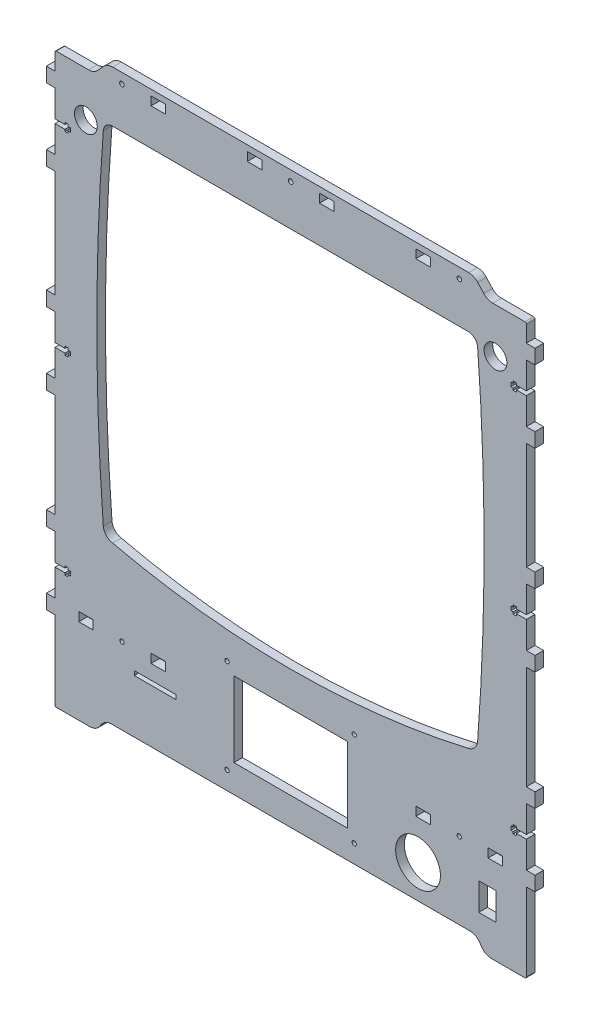
SolidWorks part; units mm, degrees
ref_plane "Спереди" through (0, 0, 0) normal (0, 0, 1) x (1, 0, 0)
ref_plane "Сверху" through (0, 0, 0) normal (0, 1, 0) x (1, 0, 0)
ref_plane "Справа" through (0, 0, 0) normal (1, 0, 0) x (0, 0, -1)
sketch "Эскиз1" plane through (0, 0, 0) normal (0, 0, 1) x (1, 0, 0)
  line L0 (-95.8892, 197.3491) -> (-85.8892, 197.3491)
  line L1 (-85.8892, 197.3491) -> (-85.8892, 191.3491)
  line L2 (-85.8892, 191.3491) -> (-95.8892, 191.3491)
  line L3 (-95.8892, 191.3491) -> (-95.8892, 197.3491)
  line L4 (97.3908, 191.3491) -> (87.3908, 191.3491)
  line L5 (87.3908, 191.3491) -> (87.3908, 197.3491)
  line L6 (87.3908, 197.3491) -> (97.3908, 197.3491)
  line L7 (97.3908, 197.3491) -> (97.3908, 191.3491)
  line L8 (97.3654, -142.8875) -> (87.3654, -142.8875)
  line L9 (87.3654, -142.8875) -> (87.3654, -136.6877)
  line L10 (87.3654, -136.6877) -> (97.3654, -136.6877)
  line L11 (97.3654, -136.6877) -> (97.3654, -142.8875)
  line L12 (147.3854, -142.8884) -> (137.3854, -142.8884)
  line L13 (137.3854, -142.8884) -> (137.3854, -136.6877)
  line L14 (137.3854, -136.6877) -> (147.3854, -136.6877)
  line L15 (147.3854, -136.6877) -> (147.3854, -142.8884)
  line L16 (-135.8946, -142.8871) -> (-145.8946, -142.8871)
  line L17 (-145.8946, -142.8871) -> (-145.8946, -136.6873)
  line L18 (-145.8946, -136.6873) -> (-135.8946, -136.6873)
  line L19 (-135.8946, -136.6873) -> (-135.8946, -142.8871)
  line L20 (-85.8746, -142.8871) -> (-95.8746, -142.8871)
  line L21 (-95.8746, -142.8871) -> (-95.8746, -136.6873)
  line L22 (-95.8746, -136.6873) -> (-85.8746, -136.6873)
  line L23 (-85.8746, -136.6873) -> (-85.8746, -142.8871)
  line L24 (-19.2392, 191.3491) -> (-29.2392, 191.3491)
  line L25 (-29.2392, 191.3491) -> (-29.2392, 197.3491)
  line L26 (-29.2392, 197.3491) -> (-19.2392, 197.3491)
  line L27 (-19.2392, 197.3491) -> (-19.2392, 191.3491)
  line L28 (30.7408, 191.3491) -> (20.7408, 191.3491)
  line L29 (20.7408, 191.3491) -> (20.7408, 197.3491)
  line L30 (20.7408, 197.3491) -> (30.7408, 197.3491)
  line L31 (30.7408, 197.3491) -> (30.7408, 191.3491)
  line L32 (-122.3991, 165.873) -> (123.6241, 165.873)
  line L33 (40.0454, -173.6357) -> (40.0454, -121.6361)
  line L34 (40.0454, -121.6361) -> (-38.5546, -121.6361)
  line L35 (-38.5546, -121.6361) -> (-38.5546, -173.6357)
  line L36 (-38.5546, -173.6357) -> (40.0454, -173.6357)
  line L37 (142.9388, -159.6762) -> (142.9388, -178.6762)
  line L38 (142.9388, -178.6762) -> (130.9388, -178.6762)
  line L39 (130.9388, -178.6762) -> (130.9388, -159.6762)
  line L40 (130.9388, -159.6762) -> (142.9388, -159.6762)
  line L41 (-162.3492, -146.9309) -> (-168.3546, -146.9309)
  line L42 (-168.3546, -146.9309) -> (-168.3546, -136.9309)
  line L43 (-168.3546, -136.9309) -> (-162.3546, -136.9309)
  line L44 (-162.3546, -136.9309) -> (-162.3546, -118.3209)
  line L45 (-162.3546, -96.9409) -> (-168.3546, -96.9409)
  line L46 (-168.3546, -96.9409) -> (-168.3546, -86.9409)
  line L47 (-168.3546, -86.9409) -> (-162.3546, -86.9409)
  line L48 (-162.3546, -86.9409) -> (-162.3546, -15.2109)
  line L49 (-162.3546, -15.2109) -> (-168.3546, -15.2109)
  line L50 (-162.3546, 34.7891) -> (-168.3546, 34.7891)
  line L51 (-168.3546, -5.2109) -> (-162.3546, -5.2109)
  line L52 (-168.3546, 44.7891) -> (-162.3546, 44.7891)
  line L56 (-162.3546, 128.9491) -> (-162.3546, 147.5491)
  line L57 (-162.3492, 168.9491) -> (-168.3492, 168.9491)
  line L58 (-168.3492, 168.9491) -> (-168.3492, 178.9491)
  line L59 (-168.3492, 178.9491) -> (-162.3492, 178.9491)
  line L60 (-162.3492, 178.9491) -> (-162.3492, 190.3491)
  line L61 (-162.3492, -200.9709) -> (-162.3492, -146.9309)
  line L62 (163.8454, -146.9309) -> (169.8454, -146.9309)
  line L63 (169.8454, -146.9309) -> (169.8454, -136.9309)
  line L64 (169.8454, -136.9309) -> (163.8513, -136.9309)
  line L65 (163.8513, -136.9309) -> (163.8513, -118.3209)
  line L66 (163.9392, -96.9409) -> (169.8512, -96.9409)
  line L67 (169.8512, -96.9409) -> (169.8512, -86.9409)
  line L68 (169.8512, -86.9409) -> (163.8512, -86.9409)
  line L69 (163.8512, -86.9409) -> (163.8512, -15.2109)
  line L70 (163.8512, -15.2109) -> (169.8512, -15.2109)
  line L71 (163.8512, 34.7891) -> (169.8512, 34.7891)
  line L72 (169.8512, -5.2109) -> (163.8512, -5.2109)
  line L73 (169.8512, 44.7891) -> (163.8512, 44.7891)
  line L74 (163.8512, 118.9491) -> (169.8512, 118.9491)
  line L75 (169.8512, 118.9491) -> (169.8512, 128.9491)
  line L76 (169.8512, 128.9491) -> (163.8512, 128.9491)
  line L77 (163.8512, 128.9491) -> (163.8512, 147.5491)
  line L78 (163.8508, 168.9491) -> (169.8508, 168.9491)
  line L79 (169.8508, 168.9491) -> (169.8508, 178.9491)
  line L80 (169.8508, 178.9491) -> (163.8508, 178.9491)
  line L81 (163.8508, 178.9491) -> (163.8508, 190.3491)
  line L82 (156.9388, 150.3491) -> (156.9388, 151.7492)
  line L83 (163.9392, -115.5209) -> (156.9392, -115.5209)
  line L84 (156.9392, -114.1224) -> (154.7382, -114.1224)
  line L85 (156.9399, -118.3209) -> (163.8513, -118.3209)
  line L86 (153.2384, -118.3222) -> (154.7405, -118.3222)
  line L87 (-155.4441, 11.989) -> (-153.2432, 11.989)
  line L88 (154.7382, -114.1224) -> (154.7382, -115.5222)
  line L89 (154.7391, 16.1893) -> (153.24, 16.1893)
  line L90 (153.2384, -115.5222) -> (153.2384, -118.3222)
  line L91 (-155.4426, -119.721) -> (-153.2418, -119.721)
  line L92 (163.8508, 150.3491) -> (156.9388, 150.3491)
  line L93 (156.9399, -119.7231) -> (156.9399, -118.3209)
  line L94 (156.9392, -115.5209) -> (156.9392, -114.1224)
  line L95 (154.7382, -115.5222) -> (153.2384, -115.5222)
  line L96 (154.741, 147.5502) -> (154.741, 146.1493)
  line L97 (-155.4451, -114.1209) -> (-155.4451, -115.5209)
  line L98 (154.7415, 13.3902) -> (154.7415, 11.9893)
  line L99 (-162.3546, 147.5491) -> (-155.4441, 147.5491)
  line L100 (-155.4441, 147.5491) -> (-155.4441, 146.149)
  line L101 (-155.4398, 150.3491) -> (-162.3492, 150.3491)
  line L102 (-153.2398, 150.3482) -> (-153.2398, 151.7491)
  line L103 (154.7405, -118.3222) -> (154.7405, -119.7231)
  line L104 (-155.4451, -115.5209) -> (-162.3546, -115.5209)
  line L105 (154.741, 151.7492) -> (154.741, 150.3493)
  line L106 (156.9417, 146.1493) -> (156.9417, 147.5491)
  line L107 (-153.2432, 13.3622) -> (-151.7428, 13.3622)
  line L108 (-155.4426, -118.3209) -> (-155.4426, -119.721)
  line L109 (153.241, 150.3493) -> (153.241, 147.5502)
  line L110 (-153.2451, 17.5891) -> (-155.4451, 17.5891)
  line L111 (-162.3546, 13.3891) -> (-155.4441, 13.3891)
  line L112 (154.741, 146.1493) -> (156.9417, 146.1493)
  line L113 (153.241, 147.5502) -> (154.741, 147.5502)
  line L114 (-153.2433, 147.5489) -> (-151.7375, 147.5489)
  line L115 (-151.7428, 13.3622) -> (-151.7428, 16.1885)
  line L116 (163.8512, 16.1891) -> (156.9392, 16.1891)
  line L117 (154.7391, 17.5621) -> (154.7391, 16.1893)
  line L118 (154.741, 150.3493) -> (153.241, 150.3493)
  line L119 (154.7415, 11.9893) -> (156.9417, 11.9893)
  line L120 (-153.2451, -114.1209) -> (-155.4451, -114.1209)
  line L121 (-151.7436, -118.3211) -> (-151.7436, -115.5218)
  line L122 (-153.2418, -118.3211) -> (-151.7436, -118.3211)
  line L123 (-153.2432, 11.989) -> (-153.2432, 13.3622)
  line L124 (156.9417, 13.3891) -> (163.8512, 13.3891)
  line L125 (-162.3546, -118.3209) -> (-155.4426, -118.3209)
  line L126 (153.24, 16.1893) -> (153.24, 13.3902)
  line L127 (-153.2451, -115.5218) -> (-153.2451, -114.1209)
  line L128 (-151.7428, 16.1885) -> (-153.2451, 16.1885)
  line L129 (-155.4441, 146.149) -> (-153.2433, 146.149)
  line L130 (-153.2418, -119.721) -> (-153.2418, -118.3211)
  line L131 (-155.4398, 151.7491) -> (-155.4398, 150.3491)
  line L132 (-151.7436, -115.5218) -> (-153.2451, -115.5218)
  line L133 (-153.2433, 146.149) -> (-153.2433, 147.5489)
  line L134 (153.24, 13.3902) -> (154.7415, 13.3902)
  line L135 (156.9388, 151.7492) -> (154.741, 151.7492)
  line L136 (-151.7375, 147.5489) -> (-151.738, 150.3482)
  line L137 (156.9417, 147.5491) -> (163.8512, 147.5491)
  line L138 (-155.4451, 16.1891) -> (-162.3546, 16.1891)
  line L139 (156.9417, 11.9893) -> (156.9417, 13.3891)
  line L140 (-155.4451, 17.5891) -> (-155.4451, 16.1891)
  line L141 (154.7405, -119.7231) -> (156.9399, -119.7231)
  line L142 (-153.2398, 151.7491) -> (-155.4398, 151.7491)
  line L143 (156.9392, 17.5621) -> (154.7391, 17.5621)
  line L144 (-151.738, 150.3482) -> (-153.2398, 150.3482)
  line L145 (-162.3546, -115.5209) -> (-162.3546, -96.9409)
  line L146 (-162.3492, 150.3491) -> (-162.3492, 168.9491)
  line L147 (163.9392, -115.5209) -> (163.9392, -96.9409)
  line L148 (163.8508, 150.3491) -> (163.8508, 168.9491)
  line L149 (-139.0924, 191.3491) -> (-161.5253, 191.3491)
  line L150 (-128.7242, 198.5879) -> (-132.8221, 194.1104)
  line L151 (123.9554, 201.3491) -> (-122.4539, 201.3491)
  line L152 (130.2257, 198.5879) -> (134.3236, 194.1104)
  line L153 (140.5939, 191.3491) -> (162.8508, 191.3491)
  line L154 (-131.8015, -198.9146) -> (-129.7448, -195.8949)
  line L155 (162.7628, -201.9477) -> (139.7264, -201.9477)
  line L156 (133.303, -198.9146) -> (131.2463, -195.8949)
  line L157 (-161.4373, -201.9509) -> (-138.3129, -201.9509)
  line L158 (-123.2334, -192.8586) -> (124.7349, -192.8586)
  line L159 (163.8454, -200.9731) -> (163.8454, -146.9309)
  line L160 (-162.3546, 13.3891) -> (-162.3546, -5.2109)
  line L161 (-168.3546, -15.2109) -> (-168.3546, -5.2109)
  line L162 (-168.3546, 34.7891) -> (-168.3546, 44.7891)
  line L163 (-162.3546, 44.7891) -> (-162.3546, 118.9491)
  line L164 (163.8512, 13.3891) -> (163.8512, -5.2109)
  line L165 (169.8512, -15.2109) -> (169.8512, -5.2109)
  line L166 (169.8512, 34.7891) -> (169.8512, 44.7891)
  line L167 (163.8512, 44.7891) -> (163.8512, 118.9491)
  line L168 (-155.4441, 13.3891) -> (-155.4441, 11.989)
  line L169 (-153.2451, 16.1885) -> (-153.2451, 17.5891)
  line L170 (156.9392, 16.1891) -> (156.9392, 17.5621)
  line L171 (-162.3546, 34.7891) -> (-162.3546, 16.1891)
  line L172 (163.8512, 34.7891) -> (163.8512, 16.1891)
  line L173 (-107.5042, -155.9271) -> (-107.5042, -152.9271)
  line L174 (-107.5042, -152.9271) -> (-78.5042, -152.9271)
  line L175 (-78.5042, -152.9271) -> (-78.5042, -155.9271)
  line L176 (-78.5042, -155.9271) -> (-107.5042, -155.9271)
  line L177 (-162.3546, 128.9491) -> (-168.3546, 128.9491)
  line L178 (-162.3546, 118.9491) -> (-168.3546, 118.9491)
  line L179 (-168.3546, 118.9491) -> (-168.3546, 128.9491)
  arc A0 (-122.4711, -84.0153) -> (123.6489, -84.0153) centre (0.5889, 449.8336) ccw
  arc A1 (-128.9341, 159.8968) -> (-128.9472, -76.974) centre (1428.6282, 41.3753) ccw
  arc A2 (130.1254, -76.9742) -> (130.1588, 159.8968) centre (-1430.5029, 41.6814) ccw
  circle A3 centre (44.7454, -115.1361) radius 1.5
  circle A4 centre (44.7454, -180.3857) radius 1.5
  circle A5 centre (-43.2546, -180.3857) radius 1.5
  circle A6 centre (-43.2546, -115.1361) radius 1.5
  circle A7 centre (88.8942, -169.8279) radius 15.5
  arc A8 (130.1588, 159.8968) -> (123.6241, 165.873) centre (123.6241, 159.3123) ccw
  arc A9 (-122.3991, 165.873) -> (-128.9341, 159.8968) centre (-122.472, 159.3916) ccw
  arc A10 (-128.9472, -76.974) -> (-122.4711, -84.0153) centre (-121.245, -76.3888) ccw
  arc A11 (123.6489, -84.0153) -> (130.1254, -76.9742) centre (121.7477, -75.7674) ccw
  circle A12 centre (0.7508, 194.3491) radius 1.6
  circle A13 centre (-116.0492, 194.3491) radius 1.6
  arc A14 (134.3236, 194.1104) -> (140.5939, 191.3491) centre (140.5939, 199.8491) ccw
  arc A15 (-161.5253, 191.3491) -> (-162.3492, 190.3491) centre (-161.4373, 190.4372) ccw
  arc A16 (-139.0924, 191.3491) -> (-132.8221, 194.1104) centre (-139.0924, 199.8491) ccw
  arc A17 (-122.4539, 201.3491) -> (-128.7242, 198.5879) centre (-122.4539, 192.8491) ccw
  circle A18 centre (117.5508, 194.3491) radius 1.6
  arc A19 (130.2257, 198.5879) -> (123.9554, 201.3491) centre (123.9554, 192.8491) ccw
  arc A20 (163.8508, 190.3491) -> (162.8508, 191.3491) centre (162.8508, 190.3491) ccw
  arc A21 (-123.2334, -192.8586) -> (-129.7448, -195.8949) centre (-123.2334, -201.3586) ccw
  arc A22 (-138.3129, -201.9509) -> (-131.8015, -198.9146) centre (-138.3129, -193.4509) ccw
  arc A23 (131.2463, -195.8949) -> (124.7349, -192.8586) centre (124.7349, -201.3586) ccw
  arc A24 (133.303, -198.9146) -> (139.7264, -201.9477) centre (139.7677, -193.542) ccw
  arc A25 (-162.3492, -200.9709) -> (-161.4373, -201.9509) centre (-161.3926, -200.9949) ccw
  arc A26 (162.7628, -201.9477) -> (163.8454, -200.9731) centre (162.8028, -200.9035) ccw
  circle A27 centre (-140.9992, 160.3491) radius 7.9
  circle A28 centre (142.5008, 160.3491) radius 7.9
  circle A29 centre (-115.9946, -139.8189) radius 1.5
  circle A30 centre (117.4854, -139.8081) radius 1.5
  point P239 (87.3908, 194.3491)
  dimension "D11" = 15.8
  dimension "D12" = 15.8
  dimension "D53" = 31
  dimension "D88" = 283.5
  dimension "D1" = 10
  dimension "D2" = 12.4
  dimension "D3" = 12.4
  dimension "D4" = 10
  dimension "D5" = 18.6
  dimension "D6" = 2.8
  dimension "D7" = 18.6
  dimension "D8" = 10
  dimension "D9" = 10
  dimension "D10" = 10
  dimension "D13" = 6
  dimension "D14" = 18.6
  dimension "D15" = 18.6
  dimension "D16" = 10
  dimension "D17" = 74.16
  dimension "D18" = 74.16
  dimension "D19" = 10
  dimension "D20" = 10
  dimension "D21" = 18.6
  dimension "D22" = 18.6
  dimension "D23" = 18.6
  dimension "D24" = 18.6
  dimension "D25" = 10
  dimension "D26" = 10
  dimension "D27" = 71.73
  dimension "D28" = 71.73
  dimension "D29" = 10
  dimension "D30" = 10
  dimension "D31" = 18.58
  dimension "D32" = 18.58
  dimension "D33" = 18.61
  dimension "D34" = 18.61
  dimension "D35" = 10
  dimension "D36" = 10
  dimension "D37" = 54.04
  dimension "D38" = 54.0422
  dimension "D39" = 403.2968
  dimension "D40" = 2.8
  dimension "D41" = 2.8
  dimension "D42" = 2.8
  dimension "D43" = 2.8
  dimension "D44" = 403.3
  dimension "D45" = 10
  dimension "D46" = 10
  dimension "D47" = 10
  dimension "D48" = 169.1
  dimension "D49" = 10
  dimension "D50" = 10
  dimension "D51" = 10
  dimension "D52" = 10
  dimension "D54" = 338.2
  dimension "D55" = 169.1
  dimension "D56" = 10
  dimension "D57" = 52.3
  dimension "D58" = 52.3
  dimension "D59" = 72.46
  dimension "D60" = 72.46
  dimension "D61" = 56.65
  dimension "D62" = 56.65
  dimension "D63" = 19.99
  dimension "D64" = 19.99
  dimension "D65" = 21.35
  dimension "D66" = 21.35
  dimension "D67" = 22.46
  dimension "D68" = 22.46
  dimension "D69" = 19.9
  dimension "D70" = 19.9
  dimension "D71" = 20.12
  dimension "D72" = 20.12
  dimension "D73" = 47.32
  dimension "D74" = 78.6
  dimension "D75" = 47.32
  dimension "D76" = 4.7
  dimension "D77" = 4.7
  dimension "D78" = 4.7
  dimension "D79" = 4.7
  dimension "D80" = 6.5
  dimension "D81" = 6.5
  dimension "D84" = 55.02
  dimension "D85" = 6
  dimension "D86" = 29
  dimension "D87" = 3
  dimension "D89" = 4
  dimension "D90" = 7
  dimension "D91" = 6
  dimension "D92" = 4
  dimension "D93" = 6
  dimension "D94" = 7
  dimension "D95" = 4
  dimension "D96" = 6
  dimension "D97" = 4
  dimension "D98" = 2.8
  dimension "D99" = 7
  dimension "D100" = 31
  dimension "D101" = 31
  dimension "D102" = 166.56
  dimension "D103" = 131.73
  dimension "D104" = 51.9996
extrude "Бобышка-Вытянуть2" add sketch "Эскиз1" along normal blind 6 contours A5 | A4 | A3 | A13 | A12 | A7 | A6 | L32 A8 A2 A11 A0 A10 A1 A9 | A18 | A30 | A29 | A28 | A27 | L4 L5 L6 L7 | L0 L1 L2 L3 | L20 L21 L22 L23 | L16 L17 L18 L19 | L12 L13 L14 L15 | L8 L9 L10 L11 | L37 L38 L39 L40 | L33 L34 L35 L36 | L28 L29 L30 L31 | L24 L25 L26 L27 | L41 L42 L43 L44 L125 L108 L91 L130 L122 L121 L132 L127 L120 L97 L104 L145 L45 L46 L47 L48 L49 L161 L51 L160 L111 L168 L87 L123 L107 L115 L128 L169 L110 L140 L138 L171 L50 L162 L52 L163 L178 L179 L177 L56 L99 L100 L129 L133 L114 L136 L144 L102 L142 L131 L101 L146 L57 L58 L59 L60 A15 L149 A16 L150 A17 L151 A19 L152 A14 L153 A20 L81 L80 L79 L78 L148 L92 L82 L135 L105 L118 L109 L113 L96 L112 L106 L137 L77 L76 L75 L74 L167 L73 L166 L71 L172 L116 L170 L143 L117 L89 L126 L134 L98 L119 L139 L124 L164 L72 L165 L70 L69 L68 L67 L66 L147 L83 L94 L84 L88 L95 L90 L86 L103 L141 L93 L85 L65 L64 L63 L62 L159 A26 L155 A24 L156 A23 L158 A21 L154 A22 L157 A25 L61 | L173 L174 L175 L176
